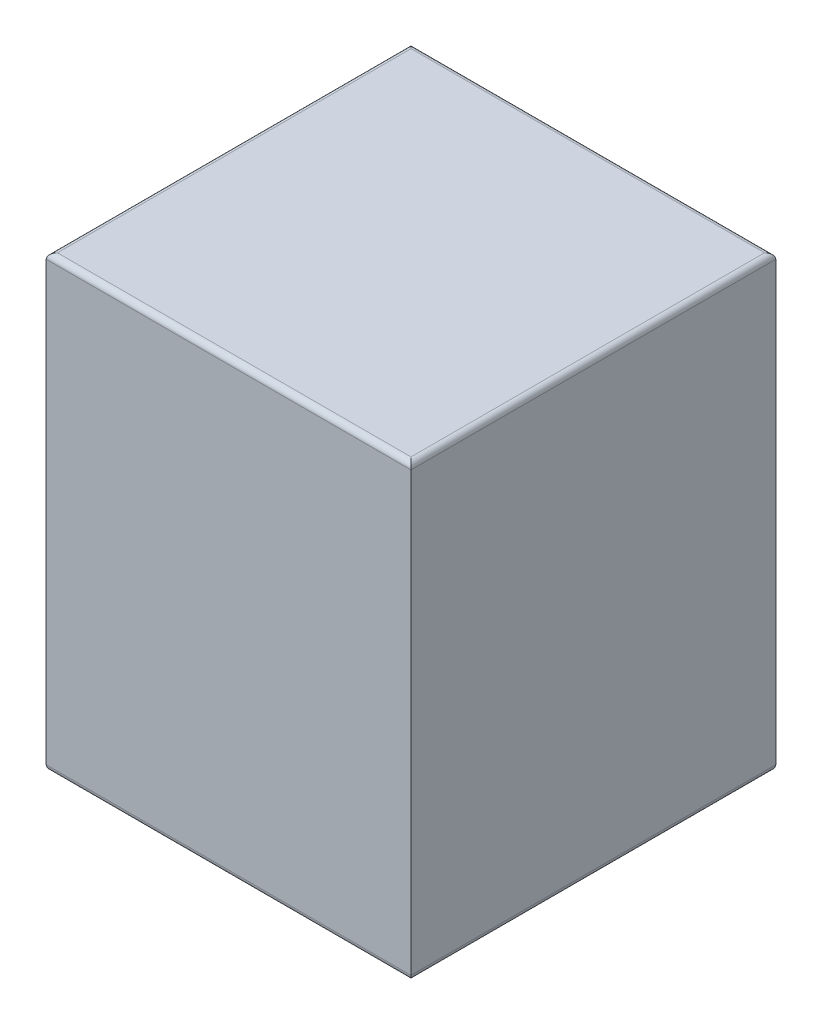
SolidWorks part; units mm, degrees
ref_plane "Front Plane" through (0, 0, 0) normal (0, 0, 1) x (1, 0, 0)
ref_plane "Top Plane" through (0, 0, 0) normal (0, 1, 0) x (1, 0, 0)
ref_plane "Right Plane" through (0, 0, 0) normal (1, 0, 0) x (0, 0, -1)
sketch "Sketch1" plane through (0, 0, 0) normal (0, 1, 0) x (1, 0, 0)
  line L0 (0, 0) -> (0, 35.6681) construction
  line L1 (-16.25, 16.25) -> (16.25, 16.25)
  line L2 (-16.25, 16.25) -> (-16.25, -16.25)
  line L3 (-16.25, -16.25) -> (16.25, -16.25)
  line L4 (16.25, 16.25) -> (16.25, -16.25)
  line L5 (0, 0) -> (45.5512, 0) construction
  dimension "D1" = 32.5
extrude "Boss-Extrude1" add sketch "Sketch1" along normal blind 40
fillet "Fillet1" radius 0.5 8 edges at (0, 0, 16.25) (16.25, 0, 0) (0, 0, -16.25) (-16.25, 0, 0) (0, 40, -16.25) (16.25, 40, 0) (0, 40, 16.25) (-16.25, 40, 0)
